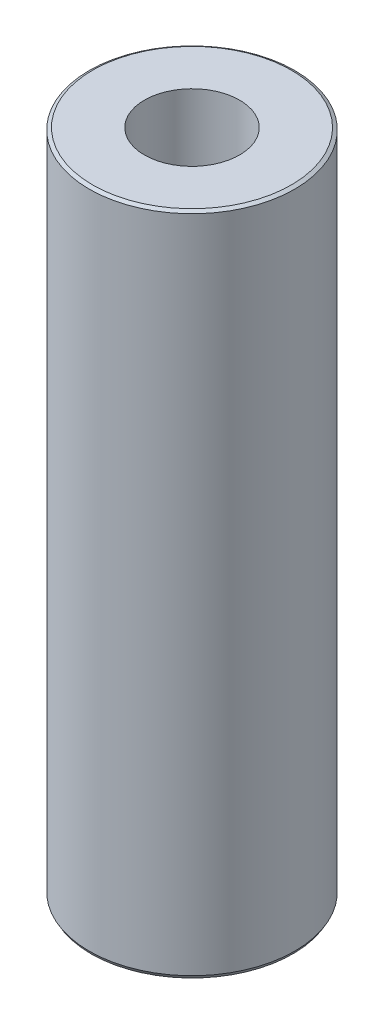
SolidWorks part; units mm, degrees
ref_plane "Front Plane" through (0, 0, 0) normal (0, 0, 1) x (1, 0, 0)
ref_plane "Top Plane" through (0, 0, 0) normal (0, 1, 0) x (1, 0, 0)
ref_plane "Right Plane" through (0, 0, 0) normal (1, 0, 0) x (0, 0, -1)
sketch "Sketch1" plane through (0, 0, 0) normal (0, 1, 0) x (1, 0, 0)
  circle A0 centre (0, 0) radius 27.5
  dimension "SHAFT_OD" = 55
extrude "Boss-Extrude1" add sketch "Sketch1" along normal blind 177.9859
sketch "Sketch2" plane through (0, 0, 0) normal (0, 1, 0) x (1, 0, 0)
  circle A0 centre (0, 0) radius 12.7259
  dimension "BORE_D" = 25.4517
extrude "Cut-Extrude1" cut sketch "Sketch2" along normal through all
chamfer "Chamfer1" distance 0.5241 angle 60 2 edges at (0, 177.9859, 27.5) (0, 0, 27.5) first distance on face at (0, 177.9859, 27.5) first distance on face at (0, 0, 12.7259)
